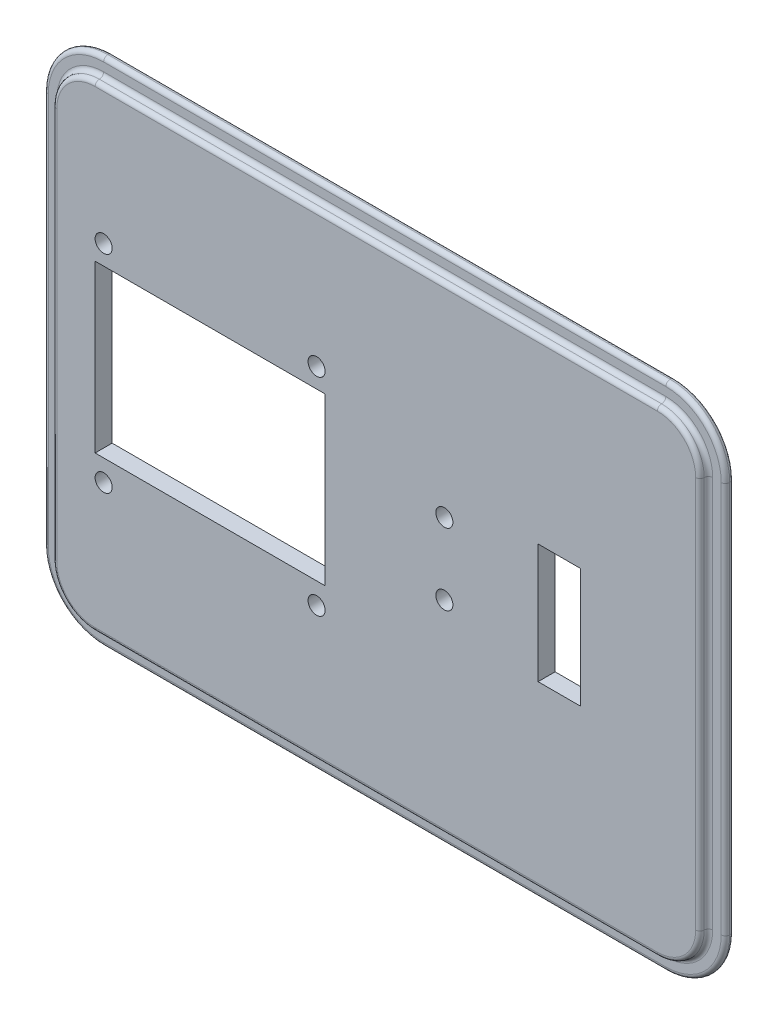
SolidWorks part; units mm, degrees
ref_plane "Plan de face" through (0, 0, 0) normal (0, 0, 1) x (1, 0, 0)
ref_plane "Plan de dessus" through (0, 0, 0) normal (0, 1, 0) x (1, 0, 0)
ref_plane "Plan de droite" through (0, 0, 0) normal (1, 0, 0) x (0, 0, -1)
sketch "Esquisse1" plane through (0, 0, 0) normal (0, 0, 1) x (1, 0, 0)
  line L0 (8, 4.2) -> (8, -4.2) construction
  line L1 (33, 30) -> (-33, 30)
  line L2 (40, 23) -> (40, -23)
  line L3 (33, -30) -> (-33, -30)
  line L4 (-40, 23) -> (-40, -23)
  line L5 (40, 30) -> (-40, -30) construction
  line L6 (40, -30) -> (-40, 30) construction
  line L7 (-33, 9.75) -> (-6, 9.75)
  line L8 (-33, 9.75) -> (-33, -9.75)
  line L9 (-33, -9.75) -> (-6, -9.75)
  line L10 (-6, 9.75) -> (-6, -9.75)
  line L11 (-33, 9.75) -> (-6, -9.75) construction
  line L12 (-33, -9.75) -> (-6, 9.75) construction
  line L13 (19, -7) -> (24, -7)
  line L14 (19, -7) -> (19, 7)
  line L15 (19, 7) -> (24, 7)
  line L16 (24, -7) -> (24, 7)
  line L17 (19, -7) -> (24, 7) construction
  line L18 (19, 7) -> (24, -7) construction
  arc A0 (33, 30) -> (40, 23) centre (33, 23) cw
  arc A1 (40, -23) -> (33, -30) centre (33, -23) cw
  arc A2 (-33, -30) -> (-40, -23) centre (-33, -23) cw
  arc A3 (-40, 23) -> (-33, 30) centre (-33, 23) cw
  circle A4 centre (-32, 12.05) radius 1
  circle A5 centre (-7, 12.05) radius 1
  circle A6 centre (-7, -12.25) radius 1
  circle A7 centre (-32, -12.25) radius 1
  circle A8 centre (8, 4.2) radius 1
  circle A9 centre (8, -4.2) radius 1
  point P0 (0, 0)
  point P18 (0, 0)
  point P34 (21.5, 0)
  point P40 (8, 0)
  point P41 (-7.6031, -10.2306)
  point P42 (-6, 0)
  point P43 (0, 0)
  dimension "D1" = 7
  dimension "D6" = 2
  dimension "D2" = 80
  dimension "D3" = 60
  dimension "D4" = 27
  dimension "D5" = 19.5
  dimension "D7" = 2.3
  dimension "D8" = 2.5
  dimension "D9" = 5
  dimension "D10" = 14
  dimension "D11" = 30
  dimension "D12" = 8.4
  dimension "D13" = 16
  dimension "D14" = 6
extrude "Boss.-Extru.1" add sketch "Esquisse1" along normal blind 2
sketch "Esquisse2" plane through (0, 0, 2) normal (0, 0, 1) x (1, 0, 0)
  line L0 (40, -23) -> (40, 23) construction
  line L1 (-33, -30) -> (33, -30) construction
  line L2 (-40, 23) -> (-40, -23) construction
  line L3 (33, 30) -> (-33, 30) construction
  line L4 (40, -23) -> (40, 23)
  line L5 (-33, -30) -> (33, -30)
  line L6 (-40, 23) -> (-40, -23)
  line L7 (33, 30) -> (-33, 30)
  line L8 (38, -23) -> (38, 23)
  line L9 (33, 28) -> (-33, 28)
  line L10 (-38, 23) -> (-38, -23)
  line L11 (-33, -28) -> (33, -28)
  arc A0 (40, 23) -> (33, 30) centre (33, 23) ccw construction
  arc A1 (33, -30) -> (40, -23) centre (33, -23) ccw construction
  arc A2 (-40, -23) -> (-33, -30) centre (-33, -23) ccw construction
  arc A3 (-33, 30) -> (-40, 23) centre (-33, 23) ccw construction
  arc A4 (40, 23) -> (33, 30) centre (33, 23) ccw
  arc A5 (33, -30) -> (40, -23) centre (33, -23) ccw
  arc A6 (-40, -23) -> (-33, -30) centre (-33, -23) ccw
  arc A7 (-33, 30) -> (-40, 23) centre (-33, 23) ccw
  arc A8 (38, 23) -> (33, 28) centre (33, 23) ccw
  arc A9 (-33, 28) -> (-38, 23) centre (-33, 23) ccw
  arc A10 (-38, -23) -> (-33, -28) centre (-33, -23) ccw
  arc A11 (33, -28) -> (38, -23) centre (33, -23) ccw
  dimension "D1" = 2
extrude "Enlèv. mat.-Extru.1" cut sketch "Esquisse2" against normal blind 1 contours A4 L7 A7 L6 A6 L5 A5 L4 | L8 A8 L9 A9 L10 A10 L11 A11
fillet "Congé1" radius 0.5 32 edges at (37.9497, 27.9497, 0) (40, 0, 0) (37.9497, -27.9497, 0) (0, -30, 0) (-37.9497, -27.9497, 0) (-40, 0, 0) (-37.9497, 27.9497, 0) (37.9497, 27.9497, 1) (40, 0, 1) (37.9497, -27.9497, 1) (0, -30, 1) (-37.9497, -27.9497, 1) (-40, 0, 1) (-37.9497, 27.9497, 1) (36.5355, 26.5355, 2) (38, 0, 2) (36.5355, -26.5355, 2) (0, -28, 2) (-36.5355, -26.5355, 2) (-38, 0, 2) (-36.5355, 26.5355, 2) (36.5355, 26.5355, 1) (38, 0, 1) (36.5355, -26.5355, 1) (0, -28, 1) (-36.5355, -26.5355, 1) (-38, 0, 1) (-36.5355, 26.5355, 1) (0, 30, 0) (0, 30, 1) (0, 28, 2) (0, 28, 1)
